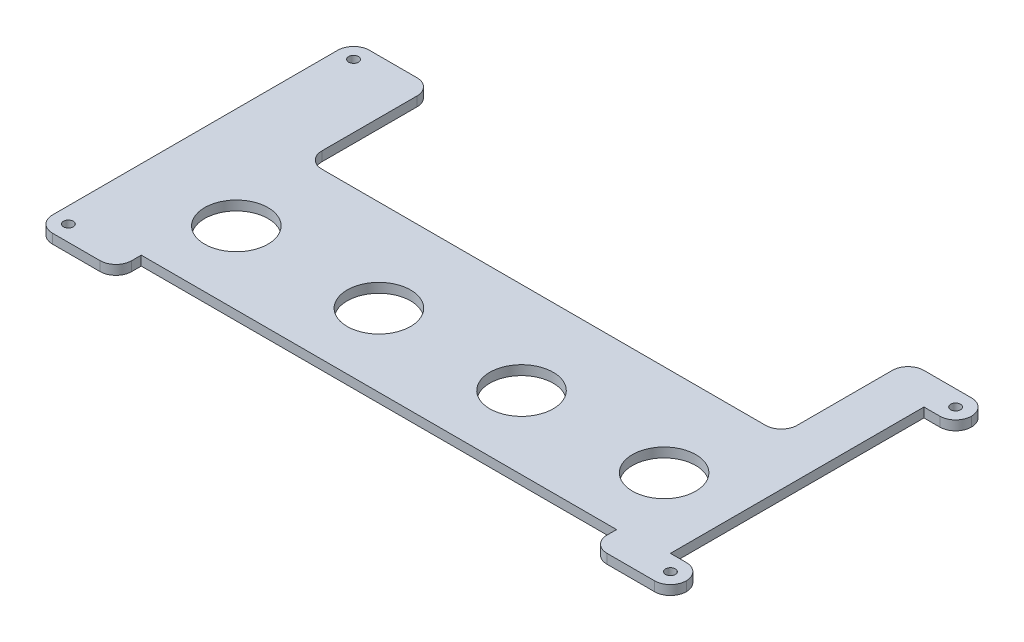
SolidWorks part; units mm, degrees
ref_plane "Front Plane" through (0, 0, 0) normal (0, 0, 1) x (1, 0, 0)
ref_plane "Top Plane" through (0, 0, 0) normal (0, 1, 0) x (1, 0, 0)
ref_plane "Right Plane" through (0, 0, 0) normal (1, 0, 0) x (0, 0, -1)
sketch "Sketch1" plane through (0, 0, 0) normal (0, 1, 0) x (1, 0, 0)
  line L1 (-100, 50) -> (100, 50)
  line L2 (-100, 50) -> (-100, -50)
  line L3 (-100, -50) -> (100, -50)
  line L4 (100, 50) -> (100, -50)
  line L5 (-100, 50) -> (100, -50) construction
  line L6 (-100, -50) -> (100, 50) construction
  point P0 (0, 0)
  dimension "D1" = 200
  dimension "D2" = 100
extrude "Boss-Extrude1" add sketch "Sketch1" along normal blind 3 contours L1 L4 L3 L2
sketch "Sketch2" plane through (0, 3, 0) normal (0, 1, 0) x (1, 0, 0)
  line L0 (-100, 50) -> (100, 50) construction
  line L1 (-100, 50) -> (-100, -50) construction
  line L2 (-100, -50) -> (100, -50) construction
  line L3 (100, 50) -> (100, -50) construction
  circle A0 centre (-95, 45) radius 1.55
  circle A1 centre (-95, -45) radius 1.55
  circle A2 centre (95, 45) radius 1.55
  circle A3 centre (95, -45) radius 1.55
  dimension "D3" = 3.1
  dimension "D4" = 3.1
  dimension "D5" = 3.1
  dimension "D6" = 3.1
  dimension "D1" = 5
  dimension "D2" = 5
  dimension "D7" = 5
  dimension "D8" = 5
  dimension "D9" = 5
  dimension "D10" = 5
  dimension "D11" = 5
  dimension "D12" = 5
extrude "Cut-Extrude1" cut sketch "Sketch2" against normal through all
fillet "Fillet1" radius 5 4 edges at (-100, 1.5, -50) (100, 1.5, -50) (100, 1.5, 50) (-100, 1.5, 50)
sketch "Sketch3" plane through (0, 3, 0) normal (0, 1, 0) x (1, 0, 0)
  line L0 (-95, 50) -> (95, 50) construction
  line L1 (-75, 50) -> (75, 50)
  line L2 (-75, 50) -> (-75, 10)
  line L3 (-75, 10) -> (75, 10)
  line L4 (75, 50) -> (75, 10)
  line L5 (-100, 45) -> (-100, -45) construction
  line L6 (100, 45) -> (100, -45) construction
  line L7 (-95, -50) -> (95, -50) construction
  line L8 (100, 40) -> (90, 40)
  line L9 (100, 40) -> (100, -40)
  line L10 (100, -40) -> (90, -40)
  line L11 (90, 40) -> (90, -40)
  line L12 (-75, -50) -> (75, -50)
  line L13 (-75, -50) -> (-75, -42)
  line L14 (-75, -42) -> (75, -42)
  line L15 (75, -50) -> (75, -42)
  line L16 (-100, -19) -> (90, -19) construction
  circle A0 centre (-68, -19) radius 10
  circle A1 centre (-23, -19) radius 10
  circle A2 centre (22, -19) radius 10
  circle A3 centre (67, -19) radius 10
  dimension "D11" = 20
  dimension "D12" = 20
  dimension "D13" = 20
  dimension "D14" = 20
  dimension "D1" = 25
  dimension "D2" = 25
  dimension "D3" = 40
  dimension "D4" = 10
  dimension "D5" = 10
  dimension "D6" = 10
  dimension "D7" = 25
  dimension "D8" = 25
  dimension "D9" = 8
  dimension "D10" = 31
  dimension "D15" = 32
  dimension "D16" = 77
  dimension "D17" = 122
  dimension "D18" = 167
extrude "Cut-Extrude2" cut sketch "Sketch3" against normal through all
fillet "Fillet2" radius 5 8 edges at (75, 1.5, -10) (75, 1.5, -50) (100, 1.5, -40) (100, 1.5, 40) (75, 1.5, 50) (-75, 1.5, 50) (-75, 1.5, -10) (-75, 1.5, -50)
